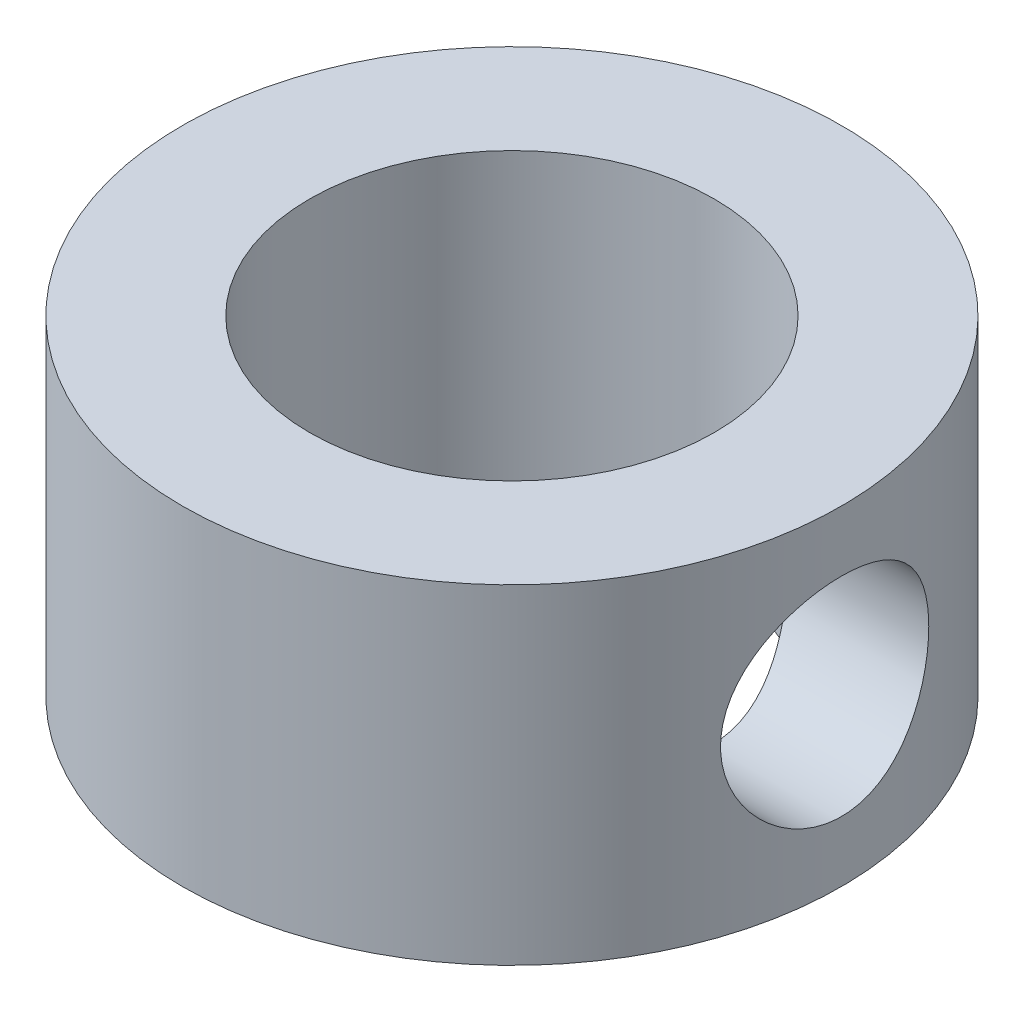
SolidWorks part; units mm, degrees
ref_plane "前视基准面" through (0, 0, 0) normal (0, 0, 1) x (1, 0, 0)
ref_plane "上视基准面" through (0, 0, 0) normal (0, 1, 0) x (1, 0, 0)
ref_plane "右视基准面" through (0, 0, 0) normal (1, 0, 0) x (0, 0, -1)
other "Configuration Table"
sketch "草图1" plane through (0, 0, 0) normal (0, 1, 0) x (1, 0, 0)
  circle A0 centre (0, 0.826) radius 3.07
  circle A1 centre (0, 0.826) radius 5
extrude "凸台-拉伸1" add sketch "草图1" along normal blind 5
sketch "草图2" plane through (0, 5, 0) normal (0, 1, 0) x (1, 0, 0)
  line L1 (-5.8299, 2.3147) -> (5.5086, 2.3147)
  line L2 (-5.8299, 2.3147) -> (-5.8299, -1.0554)
  line L3 (-5.8299, -1.0554) -> (5.5086, -1.0554)
  line L4 (5.5086, 2.3147) -> (5.5086, -1.0554)
extrude "凸台-拉伸2" add sketch "草图2" against normal blind 7 separate body
sketch "草图3" plane through (5.5086, 0, 0) normal (1, 0, 0) x (0, 0, -1)
  line L1 (-4.174, 5) -> (-4.174, 0) construction
  line L2 (-1.0554, 5) -> (2.3147, 5) construction
  circle A0 centre (0.826, 2.5) radius 1.58
  dimension "D1" = 5
  dimension "D2" = 2.5
extrude "凸台-拉伸3" add sketch "草图3" against normal blind 6 separate body
delete or keep bodies "实体-删除/保留 1" type delete bodies bodies 107
combine bodies "组合1" operation type subtract main body 106 bodies to subtract 108
